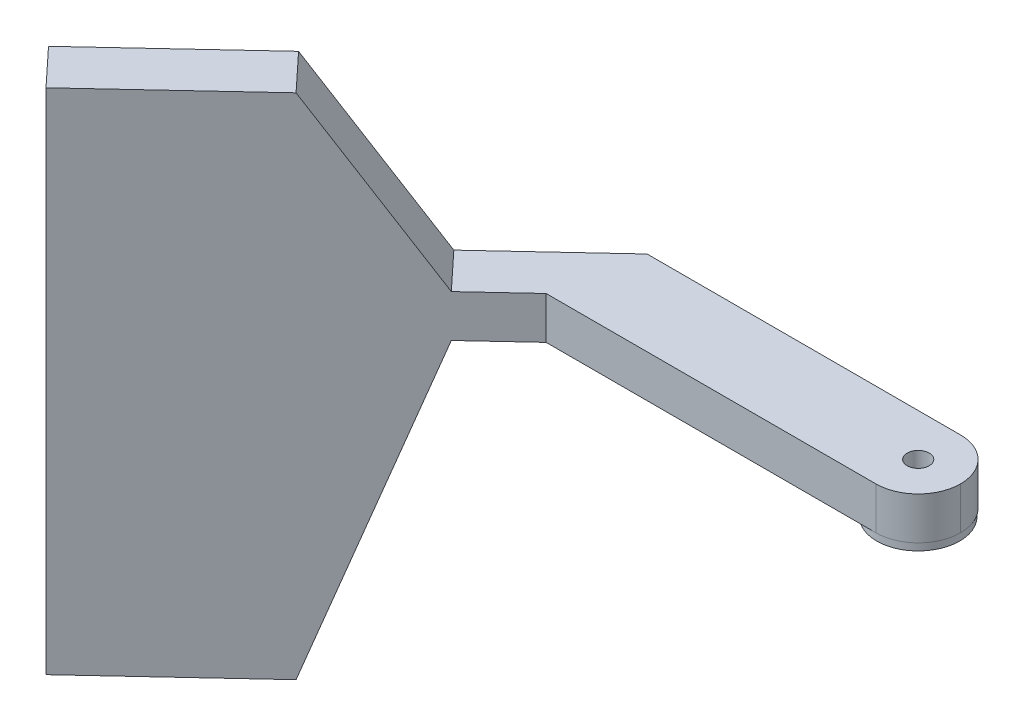
SolidWorks part; units mm, degrees
ref_plane "Front" through (0, 0, 0) normal (0, 0, 1) x (1, 0, 0)
ref_plane "Top" through (0, 0, 0) normal (0, 1, 0) x (1, 0, 0)
ref_plane "Right" through (0, 0, 0) normal (1, 0, 0) x (0, 0, -1)
sketch "Sketch1" plane through (0, 0, 0) normal (0, 1, 0) x (1, 0, 0)
  line L0 (0, 10) -> (0, 0)
  line L1 (0, 0) -> (42, 0)
  line L3 (0, 10) -> (42, 10)
  line L4 (42, 0) -> (42, 10)
  line L9 (0, 10) -> (-36.5677, -24.0999)
  line L10 (-36.5677, -24.0999) -> (-32.4757, -28.488)
  line L11 (0, 10) -> (4.092, 5.6119)
  line L12 (-32.4757, -28.488) -> (4.092, 5.6119)
  line L13 (0, 0) -> (-1.926, 0)
  line L14 (-1.926, 0) -> (0, 1.796)
  line L15 (0, 1.796) -> (0, 0)
  dimension "D1" = 10
  dimension "D2" = 42
  dimension "D3" = 223
  dimension "D4" = 50
  dimension "D5" = 6
  dimension "D6" = 270
extrude "Boss-Extrude1" add sketch "Sketch1" along normal blind 5 contours L10 L12 L1 L0 L9 | L1 L12 L11 L0 | L12 L1 L4 L3 L11 | L13 L0 L12 region at (1.364, 0, -5.8026) region at (-17.2811, 0, 10.1358) region at (21.8174, 0, -4.9666) region at (-0.642, 0, -0.5987)
fillet "Fillet1" radius 5 2 edges at (42, 2.5, 0) (42, 2.5, -10)
sketch "Sketch2" plane through (0, 5, 0) normal (0, 1, 0) x (1, 0, 0)
  circle A0 centre (37, 5) radius 1.3
extrude "Cut-Extrude1" cut sketch "Sketch2" against normal blind 10
sketch "Sketch3" plane through (0, 5, 0) normal (0, 1, 0) x (1, 0, 0)
  line L0 (-36.5677, -24.0999) -> (-32.4757, -28.488)
  line L1 (-32.4757, -28.488) -> (-17.2009, -14.244)
  line L2 (-32.4757, -28.488) -> (-1.926, 0) construction
  line L3 (-17.2009, -14.244) -> (-21.2928, -9.8559)
  line L4 (0, 10) -> (-36.5677, -24.0999) construction
  line L5 (-21.2928, -9.8559) -> (-36.5677, -24.0999)
extrude "Boss-Extrude2" add sketch "Sketch3" along normal blind 20
sketch "Sketch4" plane through (0, 0, 0) normal (0, -1, 0) x (1, 0, 0)
  line L0 (-36.5677, 24.0999) -> (-32.4757, 28.488)
  line L1 (-32.4757, 28.488) -> (-17.2009, 14.244)
  line L2 (-32.4757, 28.488) -> (-1.926, 0) construction
  line L3 (-17.2009, 14.244) -> (-21.2928, 9.8559)
  line L4 (0, -10) -> (-36.5677, 24.0999) construction
  line L5 (-21.2928, 9.8559) -> (-36.5677, 24.0999)
extrude "Boss-Extrude3" add sketch "Sketch4" along normal blind 35
sketch "Sketch5" plane through (-4.9878, 0, -5.3488) normal (-0.682, 0, -0.7314) x (-0.7314, 0, 0.682)
  line L0 (22.2943, -35) -> (22.2943, 0)
  line L1 (22.2943, 0) -> (9.3264, 0)
  line L2 (-6.82, 0) -> (22.2943, 0) construction
  line L3 (9.3264, 0) -> (22.2943, -35)
  line L4 (9.3264, 5) -> (22.2943, 25)
  line L5 (-6.82, 5) -> (22.2943, 5) construction
  line L6 (22.2943, 25) -> (22.2943, 5)
  line L7 (22.2943, 5) -> (9.3264, 5)
extrude "Boss-Extrude4" add sketch "Sketch5" against normal blind 6
sketch "Sketch6" plane through (0, 0, 0) normal (0, -1, 0) x (1, 0, 0)
  circle A0 centre (37, -5) radius 4.9
  circle A1 centre (37, -5) radius 1.3
extrude "Boss-Extrude5" add sketch "Sketch6" along normal blind 0.9
